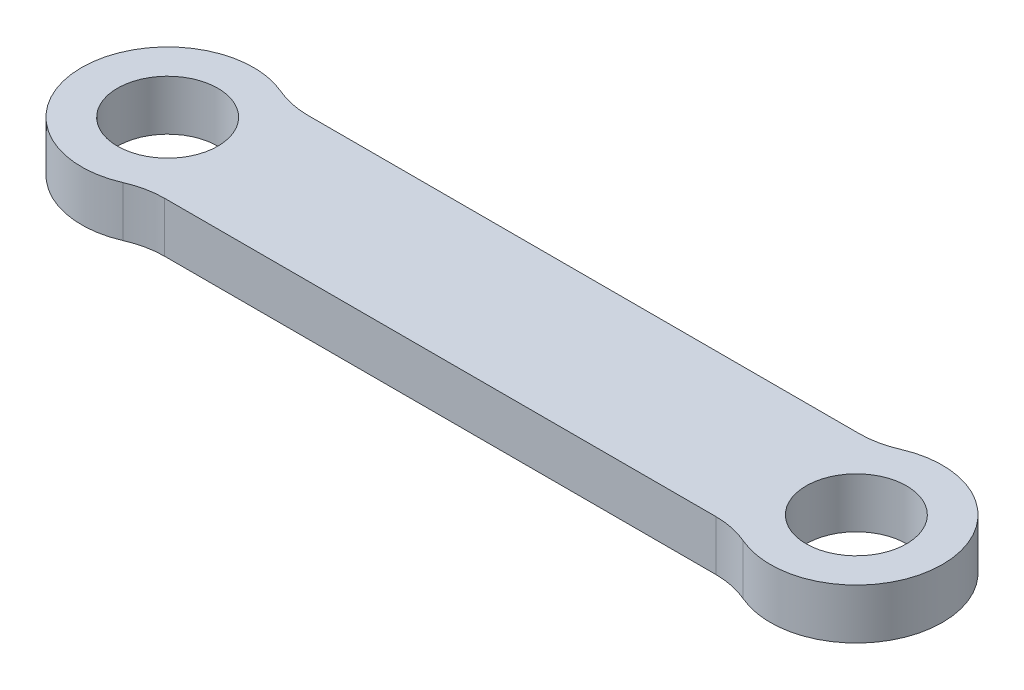
SolidWorks part; units mm, degrees
ref_plane "Front Plane" through (0, 0, 0) normal (0, 0, 1) x (1, 0, 0)
ref_plane "Top Plane" through (0, 0, 0) normal (0, 1, 0) x (1, 0, 0)
ref_plane "Right Plane" through (0, 0, 0) normal (1, 0, 0) x (0, 0, -1)
sketch "Sketch1" plane through (0, 0, 0) normal (0, 1, 0) x (1, 0, 0)
  line L0 (0, 0) -> (24, 0) construction
  line L1 (1.6583, 2.5) -> (22.3417, 2.5)
  line L2 (1.6583, -2.5) -> (22.3417, -2.5)
  circle A0 centre (0, 0) radius 3
  circle A1 centre (24, 0) radius 3
  circle A2 centre (0, 0) radius 1.75
  circle A3 centre (24, 0) radius 1.75
  dimension "D1" = 6
  dimension "D3" = 6
  dimension "D5" = 3.5
  dimension "D6" = 3.5
  dimension "D2" = 24
  dimension "D4" = 2.5
extrude "Boss-Extrude1" add sketch "Sketch1" along normal blind 1.75 contours A2 A0 | L0 A0 L2 A1 | A0 L0 A1 L1 | A1 A3 region at (2.5686, 0, 1.3785) region at (12, 0, -1.2778) region at (12, 0, 1.2778) region at (21.4314, 0, -1.3785)
fillet "Fillet1" radius 3 4 edges at (1.6583, 0.875, 2.5) (22.3417, 0.875, 2.5) (22.3417, 0.875, -2.5) (1.6583, 0.875, -2.5)
